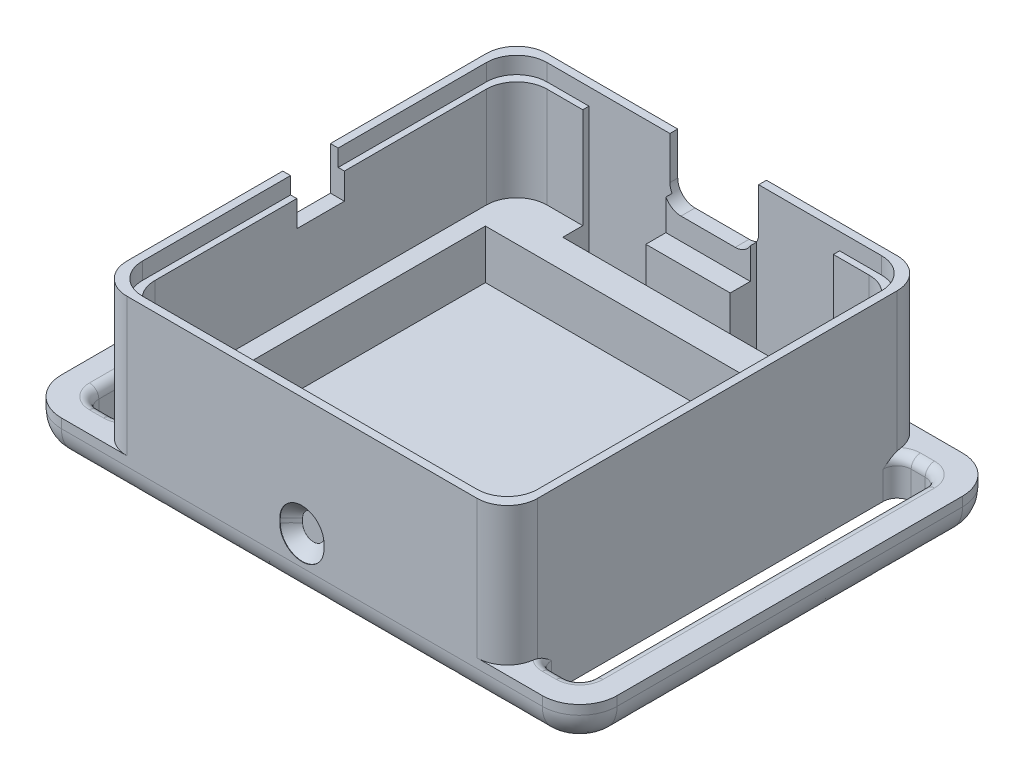
SolidWorks part; units mm, degrees
material "ABS"
ref_plane "Front Plane" through (0, 0, 0) normal (0, 0, 1) x (1, 0, 0)
ref_plane "Top Plane" through (0, 0, 0) normal (0, 1, 0) x (1, 0, 0)
ref_plane "Right Plane" through (0, 0, 0) normal (1, 0, 0) x (0, 0, -1)
sketch "Bottom base Sketch" plane through (0, 0, 0) normal (0, 1, 0) x (1, 0, 0)
  line L1 (-22, 22.5) -> (22, 22.5)
  line L2 (-22, 22.5) -> (-22, -22.5)
  line L3 (-22, -22.5) -> (22, -22.5)
  line L4 (22, 22.5) -> (22, -22.5)
  line L5 (-22, 22.5) -> (22, -22.5) construction
  line L6 (-22, -22.5) -> (22, 22.5) construction
  point P0 (0, 0)
  dimension "D1" = 44
  dimension "D2" = 45
extrude "Bottom base" add sketch "Bottom base Sketch" along normal blind 1
sketch "Side walls sketch" plane through (0, 1, 0) normal (0, 1, 0) x (1, 0, 0)
  line L0 (-22, -22.5) -> (22, -22.5) construction
  line L1 (-20.5, -21) -> (20.5, -21)
  line L2 (-20.5, -21) -> (-20.5, 21)
  line L3 (-20.5, 21) -> (20.5, 21)
  line L4 (20.5, -21) -> (20.5, 21)
  line L5 (-20.5, -21) -> (20.5, 21) construction
  line L6 (-20.5, 21) -> (20.5, -21) construction
  line L7 (22, -22.5) -> (22, 22.5) construction
  line L8 (22, 22.5) -> (-22, 22.5) construction
  line L9 (-22, 22.5) -> (-22, -22.5) construction
  line L10 (22, -22.5) -> (22, 22.5)
  line L11 (22, 22.5) -> (-22, 22.5)
  line L12 (-22, 22.5) -> (-22, -22.5)
  line L13 (-22, -22.5) -> (22, -22.5)
  line L14 (0, -21) -> (0, -22.5) construction
  line L15 (-22, 0) -> (-20.5, 0) construction
  line L16 (0, 22.5) -> (0, 21) construction
  line L17 (20.5, 0) -> (22, 0) construction
  point P0 (0, 0)
  dimension "D1" = 1.5
extrude "Side walls" add sketch "Side walls sketch" along normal up to surface (17.8 mm away)
sketch "Top plate shoulder sketch" plane through (0, 18.8, 0) normal (0, 1, 0) x (1, 0, 0)
  line L0 (21.1667, -21.6667) -> (21.1667, 21.6667)
  line L1 (21.1667, 21.6667) -> (-21.1667, 21.6667)
  line L2 (-21.1667, 21.6667) -> (-21.1667, -21.6667)
  line L3 (-21.1667, -21.6667) -> (21.1667, -21.6667)
  line L4 (20.5, -21) -> (20.5, 21)
  line L5 (20.5, 21) -> (-20.5, 21)
  line L6 (-20.5, 21) -> (-20.5, -21)
  line L7 (-20.5, -21) -> (20.5, -21)
  line L8 (20.5, -21) -> (20.5, 21)
  line L9 (20.5, 21) -> (-20.5, 21)
  line L10 (-20.5, 21) -> (-20.5, -21)
  line L11 (-20.5, -21) -> (20.5, -21)
  dimension "D2" = 0.6667
extrude "Top plate shoulder" cut sketch "Top plate shoulder sketch" against normal up to surface (1.8 mm away)
sketch "Strap Bracket Sketch" plane through (0, 0, 0) normal (0, -1, 0) x (1, 0, 0)
  line L0 (-29.75, 0) -> (-26.5, 0) construction
  line L1 (-29.75, -22.5) -> (29.75, -22.5)
  line L2 (-29.75, -22.5) -> (-29.75, 22.5)
  line L3 (-29.75, 22.5) -> (29.75, 22.5)
  line L4 (29.75, -22.5) -> (29.75, 22.5)
  line L5 (-29.75, -22.5) -> (29.75, 22.5) construction
  line L6 (-29.75, 22.5) -> (29.75, -22.5) construction
  line L8 (22, -22.5) -> (-22, -22.5) construction
  line L9 (0, -24.1163) -> (0, 24.1163) construction
  line L10 (-22, -19.25) -> (-22, 19.25) construction
  line L11 (-22, -22.5) -> (-22, 22.5) construction
  line L12 (-22, 19.25) -> (-26.5, 19.25)
  line L13 (-22, -19.25) -> (-26.5, -19.25)
  line L14 (-26.5, 19.25) -> (-26.5, 22.5) construction
  line L15 (-26.5, -19.25) -> (-26.5, -22.5) construction
  line L16 (-26.5, 19.25) -> (-26.5, -19.25)
  line L18 (-22, 19.25) -> (-22, 22.5)
  line L19 (-22, 22.5) -> (-29.75, 22.5)
  line L20 (-22, -19.25) -> (-22, -22.5)
  line L21 (-22, -22.5) -> (-29.75, -22.5)
  line L22 (29.75, -22.5) -> (29.75, 22.5)
  line L23 (22, -19.25) -> (22, -22.5)
  line L24 (22, -19.25) -> (26.5, -19.25)
  line L25 (26.5, 19.25) -> (26.5, -19.25)
  line L26 (22, 19.25) -> (26.5, 19.25)
  line L27 (22, 19.25) -> (22, 22.5)
  line L28 (22, 22.5) -> (29.75, 22.5)
  line L29 (22, -22.5) -> (29.75, -22.5)
  point P0 (0, 0)
  point P11 (0, 0)
  line M12 (22, -22.5) -> (22, 22.5)
  line M14 (-22, 22.5) -> (-22, -22.5)
  dimension "D1" = 38.5
  dimension "D3" = 4.5
  dimension "D4" = 4.5
extrude "Strap Bracket" add sketch "Strap Bracket Sketch" against normal blind 4 contours L26 L25 L24 L1 L4 L3 M12 | L16 L12 L3 L2 L1 L13 M14 region at (-27.4792, 0, 0) region at (27.4792, 0, 0)
fillet "Case fillet" radius 3.25 12 edges at (22, 11.4, 22.5) (-22, 11.4, 22.5) (21.1667, 17.9, 21.6667) (-21.1667, 17.9, 21.6667) (-20.5, 9, 21) (20.5, 9, 21) (-21.1667, 17.9, -21.6667) (-20.5, 9, -21) (-22, 11.4, -22.5) (21.1667, 17.9, -21.6667) (20.5, 9, -21) (22, 11.4, -22.5)
fillet "Inner Strap Bracket Fillets" radius 1.5 8 edges at (-22, 2, -19.25) (-22, 2, 19.25) (-26.5, 2, 19.25) (-26.5, 2, -19.25) (22, 2, -19.25) (26.5, 2, -19.25) (22, 2, 19.25) (26.5, 2, 19.25)
fillet "Outer Strap Bracket Fillets" radius 4 4 edges at (29.75, 2, -22.5) (29.75, 2, 22.5) (-29.75, 2, 22.5) (-29.75, 2, -22.5)
sketch "USB Port Hole Sketch" plane through (0, 0, -22.5) normal (0, 0, -1) x (-1, 0, 0)
  line L0 (0, 20.05) -> (0, 14.5491) construction
  line L1 (-4.75, 18.8) -> (-4.75, 14.25)
  line L2 (-2.9, 12.4) -> (2.9, 12.4)
  line L7 (-18.75, 18.8) -> (18.75, 18.8) construction
  line L8 (-4.6, 14.25) -> (-4.6, 18.8) construction
  line L9 (-4.75, 18.8) -> (4.75, 18.8)
  line L10 (4.75, 18.8) -> (4.75, 14.25)
  arc A1 (-2.9, 15.85) -> (-2.9, 12.65) centre (-2.9, 14.25) ccw construction
  arc A2 (-4.75, 14.25) -> (-2.9, 12.4) centre (-2.9, 14.25) ccw
  arc A3 (-2.9, 15.85) -> (-2.9, 12.65) centre (-2.9, 14.25) ccw construction
  arc A4 (4.75, 14.25) -> (2.9, 12.4) centre (2.9, 14.25) cw
  point P15 (-4.5, 14.25)
  point P18 (0, 18.8)
  point P21 (0, 12.4)
  dimension "D1" = 0.15
extrude "USB Port Hole" cut sketch "USB Port Hole Sketch" against normal up to surface (1.5 mm away) up to face at (0, 9, -21)
sketch "Switch Hole Sketch" plane through (-22, 0, 0) normal (-1, 0, 0) x (0, 0, 1)
  line L0 (0, 20.05) -> (0, 12.8585) construction
  line L1 (2.4, 18.8) -> (2.4, 17) construction
  line L9 (2.4, 18.8) -> (2.4, 17) construction
  line L11 (-2.4, 17) -> (-2.4, 18.8) construction
  line L12 (-2.55, 18.8) -> (-2.55, 14.2)
  line L13 (-2.55, 14.2) -> (2.55, 14.2)
  line L14 (-19.25, 18.8) -> (19.25, 18.8) construction
  line L16 (-2.15, 14.4) -> (0.15, 14.4) construction
  line L17 (-2.55, 18.8) -> (2.55, 18.8)
  line L18 (2.55, 18.8) -> (2.55, 14.2)
  line L20 (-2.4, 17) -> (-2.4, 16.6) construction
  point P18 (0, 18.8)
  point P19 (0, 14.2)
  dimension "D1" = 0.15
  dimension "D2" = 0.2
extrude "Switch Hole" cut sketch "Switch Hole Sketch" against normal up to surface (1.5 mm away) up to face at (-20.5, 9, 0)
sketch "Battery Compartment sketch" plane through (0, 1, 0) normal (0, 1, 0) x (1, 0, 0)
  line L1 (-18.6, 15.75) -> (18.6, 15.75)
  line L2 (-18.6, 15.75) -> (-18.6, -15.75)
  line L3 (-18.6, -15.75) -> (18.6, -15.75)
  line L12 (18.6, 15.75) -> (18.6, -15.75)
  line L13 (-18.6, 15.75) -> (18.6, -15.75) construction
  line L14 (-18.6, -15.75) -> (18.6, 15.75) construction
  line L18 (-20.5, 17.75) -> (-20.5, -17.75)
  line L19 (-17.25, -21) -> (17.25, -21)
  line L20 (20.5, -17.75) -> (20.5, 17.75)
  line L21 (17.25, 21) -> (-17.25, 21)
  line L22 (-20.5, 17.75) -> (-20.5, -17.75)
  line L23 (-17.25, -21) -> (17.25, -21)
  line L24 (20.5, -17.75) -> (20.5, 17.75)
  line L25 (17.25, 21) -> (-17.25, 21)
  arc A12 (-20.5, -17.75) -> (-17.25, -21) centre (-17.25, -17.75) ccw
  arc A13 (17.25, -21) -> (20.5, -17.75) centre (17.25, -17.75) ccw
  arc A14 (20.5, 17.75) -> (17.25, 21) centre (17.25, 17.75) ccw
  arc A15 (-17.25, 21) -> (-20.5, 17.75) centre (-17.25, 17.75) ccw
  arc A16 (-20.5, -17.75) -> (-17.25, -21) centre (-17.25, -17.75) ccw
  arc A17 (17.25, -21) -> (20.5, -17.75) centre (17.25, -17.75) ccw
  arc A18 (20.5, 17.75) -> (17.25, 21) centre (17.25, 17.75) ccw
  arc A19 (-17.25, 21) -> (-20.5, 17.75) centre (-17.25, 17.75) ccw
  point P2 (0, 0)
  dimension "D1" = 37.2
  dimension "D2" = 31.5
  dimension "D3" = 0
extrude "Battery Compartment" add sketch "Battery Compartment sketch" along normal blind 5.25
fillet "Comfort Fillet" radius 2.5 8 edges at (28.5784, 0, -21.3284) (29.75, 0, 0) (28.5784, 0, 21.3284) (0, 0, 22.5) (-28.5784, 0, 21.3284) (-29.75, 0, 0) (-28.5784, 0, -21.3284) (0, 0, -22.5) second distance 3 first distance on face at (-24.25, 0, 0)
fillet "Strap Fillet" radius 1 14 edges at (-22.4393, 4, 18.8107) (-24.25, 4, 19.25) (-26.0607, 4, 18.8107) (-22.4393, 4, -18.8107) (-24.25, 4, -19.25) (-26.0607, 4, -18.8107) (22.4393, 4, 18.8107) (24.25, 4, 19.25) (26.0607, 4, 18.8107) (22.4393, 4, -18.8107) (24.25, 4, -19.25) (26.0607, 4, -18.8107) (-26.5, 4, 0) (26.5, 4, 0)
sketch "Clip hole sketch" plane through (0, 0, 0) normal (0, -1, 0) x (1, 0, 0)
  line L0 (-13.22, 19.791) -> (-13.22, 20.7288) construction
  line L1 (-13.22, 20.7288) -> (-8.97, 20.7288) construction
  line L6 (-17.9167, 21.6667) -> (17.9167, 21.6667) construction
  line L7 (-17.9167, 21.6667) -> (17.9167, 21.6667) construction
  line L8 (-13.42, 21.6667) -> (-13.42, 18.8531)
  line L9 (-13.42, 18.8531) -> (-4.52, 18.8531)
  line L10 (-4.52, 18.8531) -> (-4.52, 21.6667)
  line L11 (-4.52, 21.6667) -> (-13.42, 21.6667)
  line L12 (-4.72, 19.791) -> (-13.22, 19.791) construction
  line L13 (-13.22, 19.791) -> (-13.22, 18.8531) construction
  line L14 (-13.22, 20.5083) -> (-13.22, 19.791) construction
  line L16 (-13.22, 19.791) -> (-4.72, 19.791) construction
  line L17 (-8.97, 21.6667) -> (-8.97, 19.791) construction
  line L19 (-13.22, 19.791) -> (-13.42, 19.791) construction
  dimension "D1" = 0.2
extrude "Clip hole" cut sketch "Clip hole sketch" against normal through all
sketch "Clip Holder Sketch" plane through (-4.52, 0, 0) normal (-1, 0, 0) x (0, 0, 1)
  line L2 (20.2, 2.75) -> (20.2, 9.75) construction
  line L3 (18.8531, 6.25) -> (18.8531, 0)
  line L8 (19.35, 1.625) -> (19.35, 0)
  line L10 (19.35, 0) -> (18.8531, 0)
  arc A0 (20.2, 2.75) -> (19.791, 0.7795) centre (20.6687, 1.625) ccw construction
  arc A1 (20.2, 2.75) -> (19.791, 0.7795) centre (20.6687, 1.625) ccw construction
  arc A2 (20.2, 2.8576) -> (19.35, 1.625) centre (20.6688, 1.625) ccw
  arc A3 (18.8531, 6.25) -> (20.2, 2.8576) centre (15.2545, 2.8576) cw
  dimension "D1" = 0.1
extrude "Clip Holder" add sketch "Clip Holder Sketch" along normal up to surface (8.9 mm away) up to face at (-13.42, 6.7351, 20.5435)
mirror "Clip Mirror" about plane through (0, 0, 0) normal (1, 0, 0) of "Clip hole", "Clip Holder" second plane through (0, 0, 0) second plane normal (0, 0, 1)
sketch "Middle Reinforcement Sketch" plane through (0, 6.25, 0) normal (0, 1, 0) x (1, 0, 0)
  line L0 (-4.52, -21) -> (-4.52, -18.8531)
  line L1 (-4.52, -18.8531) -> (4.52, -18.8531)
  line L2 (4.52, -18.8531) -> (4.52, -21)
  line L3 (4.52, -21) -> (-4.52, -21)
  line L4 (-10.4255, 0) -> (10.4255, 0) construction
  line L5 (4.52, 21) -> (-4.52, 21)
  line L6 (4.52, 18.8531) -> (4.52, 21)
  line L7 (-4.52, 18.8531) -> (4.52, 18.8531)
  line L8 (-4.52, 21) -> (-4.52, 18.8531)
extrude "Middle Reinforcement" add sketch "Middle Reinforcement Sketch" along normal offset from surface (3.8 mm away) 1
sketch "Clip Button Hole Sketch" plane through (0, 0, -22.5) normal (0, 0, -1) x (-1, 0, 0)
  line L0 (-2.52, 5.92) -> (-2.52, 6.38) construction
  line L1 (2.52, 6.38) -> (2.52, 5.92) construction
  line L2 (-2.52, 5.92) -> (-2.52, 6.38) construction
  line L3 (2.52, 6.38) -> (2.52, 5.92) construction
  line L4 (-2.37, 5.92) -> (-2.37, 6.38)
  line L5 (2.37, 6.38) -> (2.37, 5.92)
  arc A0 (-2.52, 5.92) -> (2.52, 5.92) centre (0, 5.92) ccw construction
  arc A1 (2.52, 6.38) -> (-2.52, 6.38) centre (0, 6.38) ccw construction
  arc A2 (-2.52, 5.92) -> (2.52, 5.92) centre (0, 5.92) ccw construction
  arc A3 (2.52, 6.38) -> (-2.52, 6.38) centre (0, 6.38) ccw construction
  arc A4 (2.37, 6.38) -> (-2.37, 6.38) centre (0, 6.38) ccw
  arc A5 (-2.37, 5.92) -> (2.37, 5.92) centre (0, 5.92) ccw
  dimension "D1" = 0.15
extrude "Clip Button Hole" cut sketch "Clip Button Hole Sketch" against normal blind 1.25
fillet "Clip Button Hole Fillet" radius 1.2 4 edges at (2.37, 6.15, -21.25) (0, 8.75, -21.25) (-2.37, 6.15, -21.25) (0, 3.55, -21.25) conic rho 0.05
mirror "Clip Button Hole Mirror" about plane through (0, 0, 0) normal (0, 0, 1) of "Clip Button Hole Fillet", "Clip Button Hole"
equation "\"wall_thickness\"= 1.5mm"
equation "\"D2@Top plate shoulder sketch\"=\"wall_thickness\" / 2.25"
equation "\"D1@Side walls sketch\"=\"wall_thickness\""
equation "\"D1@Bottom base\"=\"wall_thickness\""
equation "\"top_plate_shoulder_depth\"= 2.25mm"
